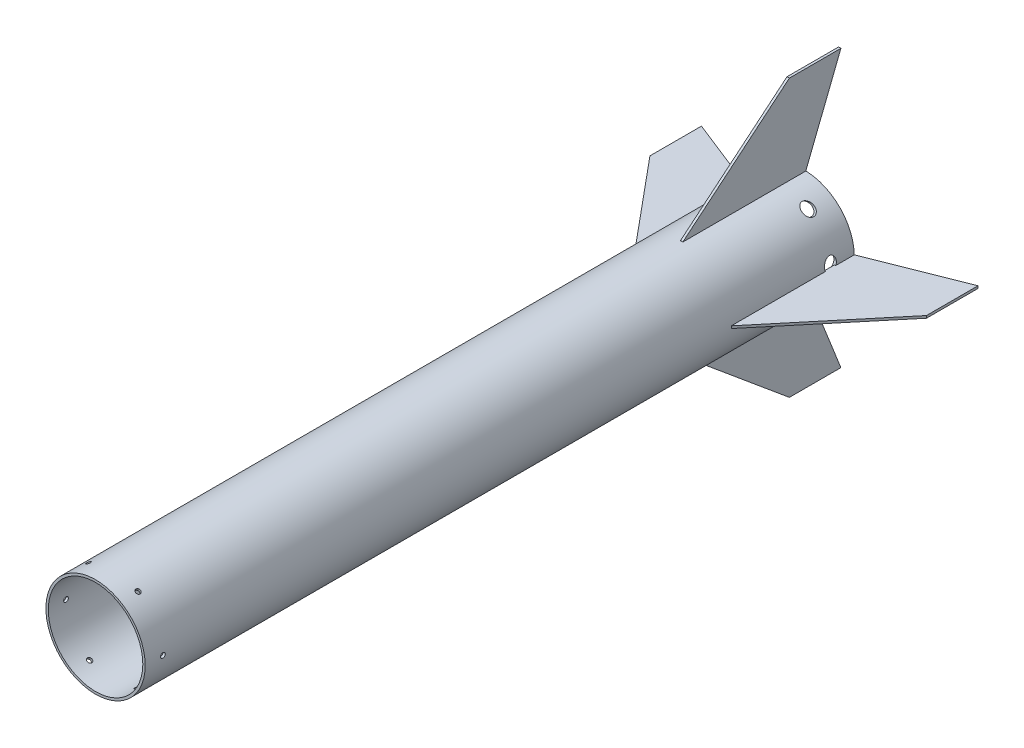
SolidWorks part; units mm, degrees
material "E-Glass Fiber"
ref_plane "Front Plane" through (0, 0, 0) normal (0, 0, 1) x (1, 0, 0)
ref_plane "Top Plane" through (0, 0, 0) normal (0, 1, 0) x (1, 0, 0)
ref_plane "Right Plane" through (0, 0, 0) normal (1, 0, 0) x (0, 0, -1)
sketch "Sketch1" plane through (0, 0, 0) normal (0, 0, 1) x (1, 0, 0)
  circle A0 centre (0, 0) radius 42
  circle A1 centre (0, 0) radius 40
  dimension "D1" = 84
  dimension "D2" = 2
extrude "Boss-Extrude1" add sketch "Sketch1" along normal blind 600
ref_plane "Bolts to Avionics" through (45, 0, 0) normal (1, 0, 0) x (0, 0, -1)
sketch "Sketch2" plane through (45, 0, 0) normal (1, 0, 0) x (0, 0, -1)
  line L0 (-600, 0) -> (-585, 0) construction
  line L1 (-600, 42) -> (-600, -42) construction
  circle A0 centre (-585, 0) radius 2
  dimension "D2" = 4
  dimension "D1" = 15
extrude "Cut-Extrude1" cut sketch "Sketch2" against normal up to surface (5 mm away) up to face at (40, 0, 600)
pattern_circular "CirPattern1" count 6 over 360 about axis through (0, 0, 600) along (0, 0, -1) of "Cut-Extrude1"
ref_plane "Tail bolts" through (-42, 0, 0) normal (-1, 0, 0) x (0, 0, 1)
sketch "Sketch4" plane through (-42, 0, 0) normal (-1, 0, 0) x (0, 0, 1)
  line L0 (0, -21.5736) -> (20, -21.5736) construction
  line L1 (0, 42) -> (0, -42) construction
  circle A0 centre (20, -21.5736) radius 5
  dimension "D2" = 10
  dimension "D1" = 20
extrude "Cut-Extrude2" cut sketch "Sketch4" against normal up to surface (8.3165 mm away) contours A0 up to face at (21.6625, 33.6264, 584.5428)
pattern_circular "CirPattern2" count 7 over 360 about axis through (0, 0, 600) along (0, 0, -1) of "Cut-Extrude2" reverse direction yes
sketch "Tail Configuration" plane through (0, 0, 0) normal (0, 0, -1) x (-1, 0, 0)
  line L0 (0, 0) -> (0, 42) construction
  line L1 (0, 0) -> (36.3731, -21) construction
  line L2 (0, 0) -> (-36.3731, -21) construction
  line L3 (31.4856, -29.4654) -> (41.2605, -12.5346) construction
  line L4 (-41.8479, -11.5173) -> (-30.8983, -30.4827) construction
  circle A0 centre (0, 0) radius 42 construction
  point P10 (0, 0)
  point P12 (36.3731, -21)
  point P15 (-36.3731, -21)
  dimension "D1" = 3
ref_plane "Fin 1" through (0, 42, 0) normal (0, 1, 0) x (1, 0, 0)
sketch "Sketch6" plane through (0, 42, 0) normal (0, 1, 0) x (1, 0, 0)
  line L4 (0, 0) -> (0, -62.2364) construction
  point P4 (0, 0)
ref_plane "Plane6" through (0, 0, 0) normal (-1, 0, 0) x (0, 0, 1)
sketch "Sketch13" plane through (0, 0, 0) normal (-1, 0, 0) x (0, 0, 1)
  line L0 (0, 42) -> (104, 42) construction
  line L1 (52.1788, 42) -> (-52.1788, 42) construction
  line L2 (104, 42) -> (13.9, 117)
  line L3 (13.9, 117) -> (-29.7, 117)
  line L4 (-29.7, 117) -> (0, 42)
  line L5 (0, 42) -> (0, 117) construction
  line L6 (78, 42) -> (78, 50.3814) construction
  line L7 (78, 42) -> (3, 117) construction
  line L9 (0, 42) -> (104, 42) construction
  line L10 (0, 42) -> (0, 41)
  line L11 (0, 41) -> (104, 41)
  line L12 (104, 42) -> (104, 41)
  dimension "D5" = 26
  dimension "D6" = 10.9
  dimension "D7" = 1
  dimension "D1" = 75
  dimension "D2" = 104
  dimension "D3" = 43.6
  dimension "D4" = 45
extrude "Boss-Extrude6" add sketch "Sketch13" along normal mid plane 2 separate body
ref_plane "Fin 2" [suppressed] through (-36.3731, -21, 0) normal (0.866, 0.5, 0) x (-0.5, 0.866, 0)
sketch "Sketch9" [suppressed] plane through (-36.3731, -21, 0) normal (0.866, 0.5, 0) x (-0.5, 0.866, 0)
  line L0 (0, 0) -> (0, 21.8091) construction
ref_plane "Plane4" [suppressed] through (0, 0, 0) normal (-0.5, 0.866, 0) x (0, 0, 1)
sketch "Sketch10" [suppressed] plane through (0, 0, 0) normal (-0.5, 0.866, 0) x (0, 0, 1)
  line L0 (0, -42) -> (-10.3999, -117)
  line L1 (-10.3999, -117) -> (33.2001, -117)
  line L2 (33.2001, -117) -> (104, -42)
  line L3 (24.967, -42) -> (600, -42) construction
  line L4 (104, -42) -> (0, -42) construction
  line L5 (78, -42) -> (78, -62.2562) construction
  line L6 (78, -42) -> (22.3001, -117) construction
  line L7 (0, -42) -> (0, -117) construction
  line L9 (0, -42) -> (104, -42) construction
  line L10 (0, -42) -> (0, -41)
  line L11 (0, -41) -> (104, -41)
  line L12 (104, -42) -> (104, -41)
  dimension "D1" = 104
  dimension "D3" = 45
  dimension "D4" = 75
  dimension "D2" = 43.6
  dimension "D5" = 26
  dimension "D6" = 10.9
  dimension "D7" = 1
extrude "Boss-Extrude7" [suppressed] add sketch "Sketch10" along normal mid plane 2
ref_plane "Fin 3" [suppressed] through (36.3731, -21, 0) normal (-0.866, 0.5, 0) x (-0.5, -0.866, 0)
sketch "Sketch11" [suppressed] plane through (36.3731, -21, 0) normal (-0.866, 0.5, 0) x (-0.5, -0.866, 0)
  line L0 (0, 0) -> (0, 29.9322) construction
ref_plane "Plane5" [suppressed] through (0, 0, 0) normal (-0.5, -0.866, 0) x (0, 0, 1)
sketch "Sketch12" [suppressed] plane through (0, 0, 0) normal (-0.5, -0.866, 0) x (0, 0, 1)
  line L0 (0, -42) -> (104, -42) construction
  line L1 (0, -42) -> (600, -42) construction
  line L2 (104, -42) -> (33.2001, -117)
  line L3 (33.2001, -117) -> (-10.3999, -117)
  line L4 (-10.3999, -117) -> (0, -42)
  line L5 (0, -42) -> (0, -117) construction
  line L6 (78, -42) -> (78, -53.3564) construction
  line L7 (78, -42) -> (22.3001, -117) construction
  line L9 (0, -42) -> (104, -42) construction
  line L10 (0, -42) -> (0, -41)
  line L11 (0, -41) -> (104, -41)
  line L12 (104, -42) -> (104, -41)
  dimension "D1" = 104
  dimension "D3" = 45
  dimension "D5" = 26
  dimension "D7" = 1
  dimension "D2" = 75
  dimension "D4" = 10.9
  dimension "D6" = 43.6
extrude "Boss-Extrude5" [suppressed] add sketch "Sketch12" along normal mid plane 2
pattern_circular "CirPattern3" count 4 over 360 about axis through (0, 0, 0) along (0, 0, 1) of "Boss-Extrude6"
fillet "Fillet5" [suppressed] radius 1
equation "\"Tip Chord\"= 43.6mm"
equation "\"Root Chord\"= 104mm"
equation "\"Height\"= 75mm"
equation "\"Sweep angle\"= 45deg"
equation "\"D1@Sketch10\"=\"Root Chord\""
equation "\"D3@Sketch10\"=\"Sweep angle\""
equation "\"D4@Sketch10\"=\"Height\""
equation "\"D2@Sketch10\"=\"Tip Chord\""
equation "\"D1@Sketch12\"=\"Root Chord\""
equation "\"D2@Sketch12\"=\"Height\""
equation "\"D3@Sketch12\"=\"Sweep angle\""
equation "\"D4@Sketch12\"=\"Tip Chord\"/4"
equation "\"D5@Sketch12\"=\"Root Chord\"/4"
equation "\"D6@Sketch12\"=\"Tip Chord\""
equation "\"D5@Sketch10\"=\"Root Chord\"/4"
equation "\"D6@Sketch10\"=\"Tip Chord\"/4"
equation "\"D1@Sketch13\"=\"Height\""
equation "\"D2@Sketch13\"=\"Root Chord\""
equation "\"D3@Sketch13\"=\"Tip Chord\""
equation "\"D4@Sketch13\"=\"Sweep angle\""
equation "\"D5@Sketch13\"=\"Root Chord\"/4"
equation "\"D6@Sketch13\"=\"Tip Chord\"/4"
